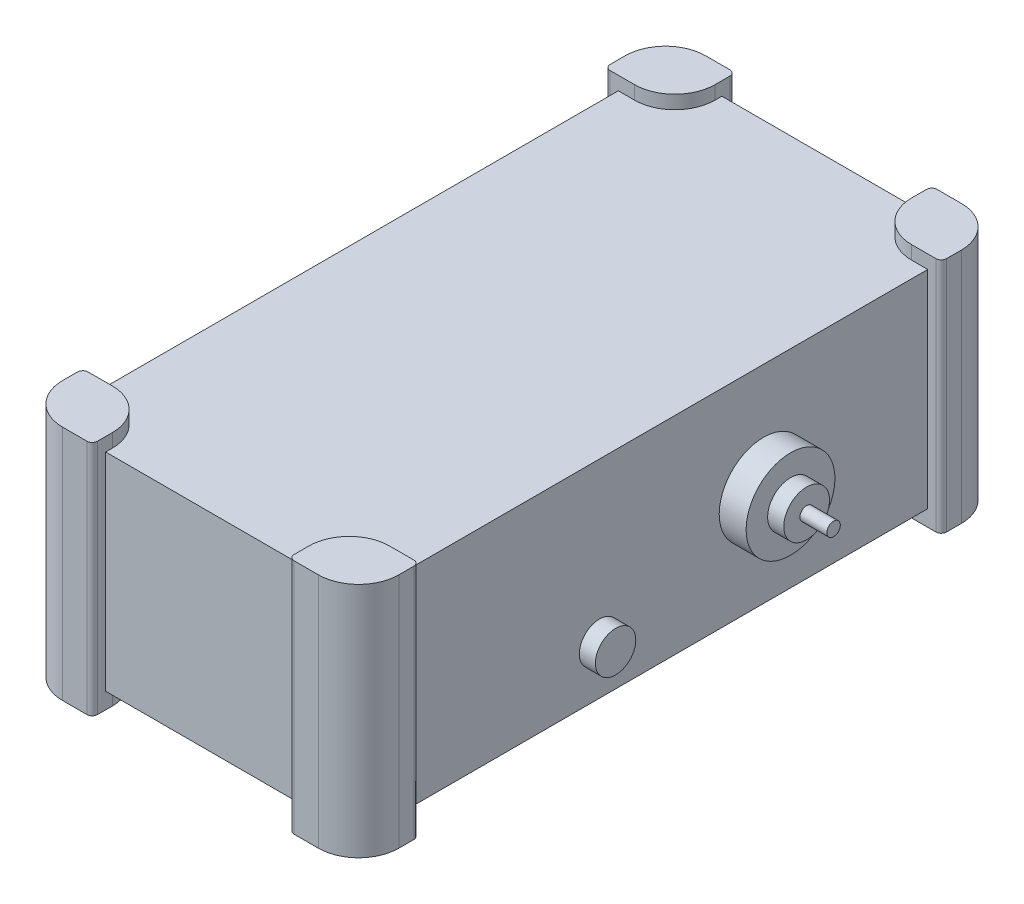
SolidWorks part; units mm, degrees
ref_plane "Front Plane" through (0, 0, 0) normal (0, 0, 1) x (1, 0, 0)
ref_plane "Top Plane" through (0, 0, 0) normal (0, 1, 0) x (1, 0, 0)
ref_plane "Right Plane" through (0, 0, 0) normal (1, 0, 0) x (0, 0, -1)
sketch "Sketch1" plane through (0, 0, 0) normal (0, 1, 0) x (1, 0, 0)
  line L1 (-57.5, 114.5) -> (57.5, 114.5)
  line L2 (-57.5, 114.5) -> (-57.5, -114.5)
  line L3 (-57.5, -114.5) -> (57.5, -114.5)
  line L4 (57.5, 114.5) -> (57.5, -114.5)
  line L5 (-57.5, 114.5) -> (57.5, -114.5) construction
  line L6 (-57.5, -114.5) -> (57.5, 114.5) construction
  point P0 (0, 0)
  dimension "D1" = 115
  dimension "D2" = 229
extrude "Boss-Extrude1" add sketch "Sketch1" along normal blind 77
sketch "Sketch12" plane through (0, 77, 0) normal (0, 1, 0) x (1, 0, 0)
  line L0 (0, 114.5) -> (0, -114.5) construction
  line L1 (57.5, 114.5) -> (-57.5, 114.5) construction
  line L2 (-57.5, -114.5) -> (57.5, -114.5) construction
  line L3 (57.5, 0) -> (-57.5, 0) construction
  line L4 (57.5, -114.5) -> (57.5, 114.5) construction
  line L5 (-57.5, 114.5) -> (-57.5, -114.5) construction
  line L6 (-36.5, -97) -> (-62.5, -97)
  line L7 (36.5, -97) -> (62.5, -97)
  line L8 (36.5, -97) -> (36.5, -119.5)
  line L9 (36.5, -119.5) -> (62.5, -119.5)
  line L10 (62.5, -97) -> (62.5, -119.5)
  line L11 (36.5, -97) -> (62.5, -119.5) construction
  line L12 (36.5, -119.5) -> (62.5, -97) construction
  line L13 (-36.5, -119.5) -> (-62.5, -97) construction
  line L14 (-36.5, -97) -> (-62.5, -119.5) construction
  line L15 (-62.5, -97) -> (-62.5, -119.5)
  line L16 (-36.5, -119.5) -> (-62.5, -119.5)
  line L17 (-36.5, -97) -> (-36.5, -119.5)
  line L18 (36.5, 97) -> (62.5, 97)
  line L19 (-36.5, 97) -> (-62.5, 97)
  line L20 (-36.5, 97) -> (-62.5, 119.5) construction
  line L21 (-36.5, 119.5) -> (-62.5, 97) construction
  line L22 (36.5, 119.5) -> (62.5, 97) construction
  line L23 (36.5, 97) -> (62.5, 119.5) construction
  line L24 (-36.5, 97) -> (-36.5, 119.5)
  line L25 (-36.5, 119.5) -> (-62.5, 119.5)
  line L26 (-62.5, 97) -> (-62.5, 119.5)
  line L27 (62.5, 97) -> (62.5, 119.5)
  line L28 (36.5, 119.5) -> (62.5, 119.5)
  line L29 (36.5, 97) -> (36.5, 119.5)
  point P12 (49.5, -108.25)
  dimension "D1" = 26
  dimension "D2" = 22.5
  dimension "D3" = 5
  dimension "D4" = 5
extrude "Boss-Extrude3" add sketch "Sketch12" along normal blind 5 and the other way blind 83 contours L25 L26 L19 L24 | L28 L27 L18 L29 | L9 L10 L7 L8 | L16 L15 L6 L17
fillet "Fillet2" radius 15 4 edges at (-62.5, 38, -119.5) (62.5, 38, -119.5) (-62.5, 38, 119.5) (62.5, 38, 119.5)
fillet "Fillet3" radius 15 8 edges at (-36.5, -3, -97) (36.5, -3, -97) (-36.5, -3, 97) (36.5, -3, 97) (36.5, 79.5, 97) (-36.5, 79.5, 97) (36.5, 79.5, -97) (-36.5, 79.5, -97)
fillet "Fillet4" radius 2 8 edges at (-62.5, 38, -97) (-36.5, 38, -119.5) (36.5, 38, -119.5) (62.5, 38, -97) (62.5, 38, 97) (36.5, 38, 119.5) (-36.5, 38, 119.5) (-62.5, 38, 97)
sketch "Sketch13" plane through (57.5, 0, 0) normal (1, 0, 0) x (0, 0, -1)
  line L0 (0, 77) -> (0, 0) construction
  line L1 (-97, 77) -> (97, 77) construction
  line L2 (-97, 38.5) -> (97, 38.5) construction
  line L3 (-97, 0) -> (-97, 77) construction
  line L4 (97, 0) -> (97, 77) construction
  line L5 (-97, 0) -> (97, 0) construction
  circle A0 centre (-25, 18) radius 7.5
  circle A1 centre (0, 18) radius 6
  circle A2 centre (36, 37) radius 16.5
  dimension "D1" = 15
  dimension "D4" = 12
  dimension "D6" = 33
  dimension "D2" = 25
  dimension "D3" = 18
  dimension "D5" = 36
  dimension "D7" = 37
extrude "Boss-Extrude4" add sketch "Sketch13" along normal blind 6 contours A0
extrude "Boss-Extrude5" add sketch "Sketch13<6>" along normal blind 10 contours A2 region at (57.5, 37, -36)
sketch "Sketch13<6>" plane through (57.5, 0, 0) normal (1, 0, 0) x (0, 0, -1) same geometry as "Sketch13"
sketch "Sketch14" plane through (67.5, 0, 0) normal (1, 0, 0) x (0, 0, -1)
  circle A0 centre (36, 37) radius 8.5
  dimension "D1" = 17
extrude "Boss-Extrude6" add sketch "Sketch14" along normal blind 6
sketch "Sketch15" plane through (73.5, 0, 0) normal (1, 0, 0) x (0, 0, -1)
  circle A0 centre (36, 37) radius 2.5
  dimension "D1" = 5
extrude "Boss-Extrude7" add sketch "Sketch15" along normal blind 10
